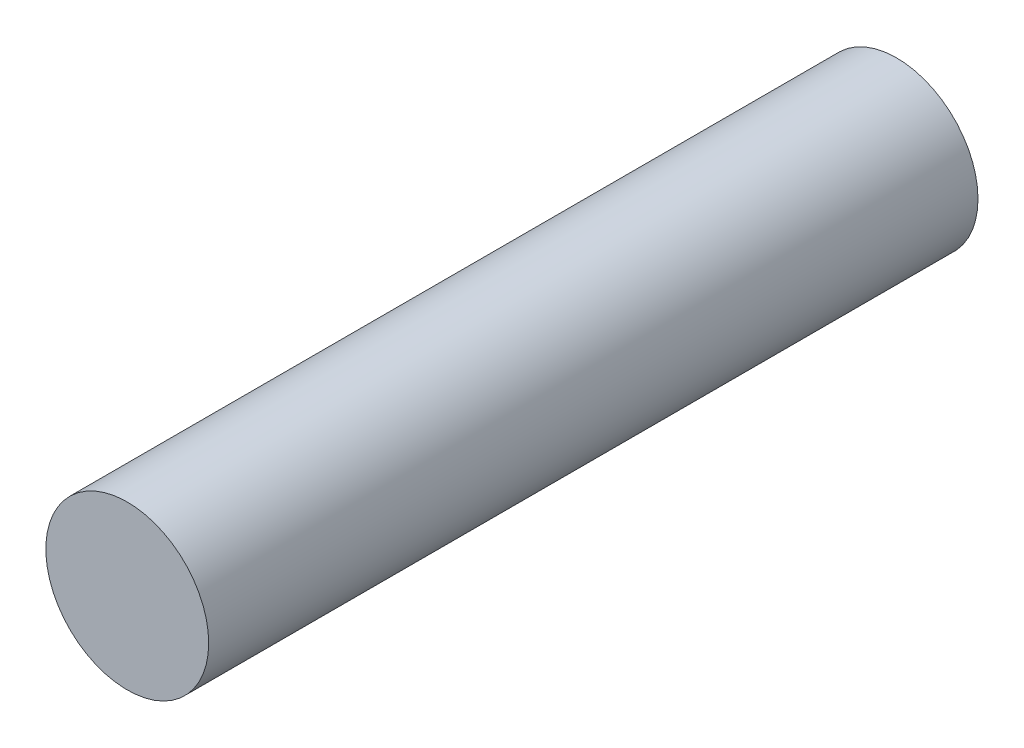
SolidWorks part; units mm, degrees
ref_plane "Front Plane" through (0, 0, 0) normal (0, 0, 1) x (1, 0, 0)
ref_plane "Top Plane" through (0, 0, 0) normal (0, 1, 0) x (1, 0, 0)
ref_plane "Right Plane" through (0, 0, 0) normal (1, 0, 0) x (0, 0, -1)
other "Configuration Table"
sketch "Sketch1" plane through (0, 0, 0) normal (0, 0, 1) x (1, 0, 0)
  circle A0 centre (0, 0) radius 12.7
  dimension "D1" = 25.4
extrude "Boss-Extrude1" add sketch "Sketch1" along normal blind 60 and the other way blind 60 contours A0
